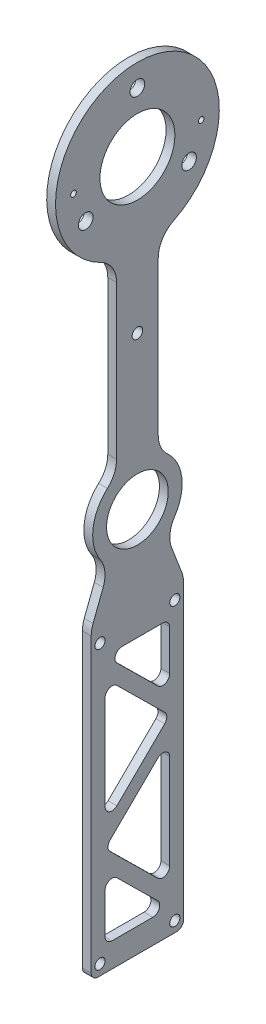
SolidWorks part; units mm, degrees
material "1060 Alloy"
ref_plane "Front Plane" through (0, 0, 0) normal (0, 0, 1) x (1, 0, 0)
ref_plane "Top Plane" through (0, 0, 0) normal (0, 1, 0) x (1, 0, 0)
ref_plane "Right Plane" through (0, 0, 0) normal (1, 0, 0) x (0, 0, -1)
sketch "Sketch1" plane through (0, 0, 0) normal (1, 0, 0) x (0, 0, -1)
  line L0 (-13.4747, 0) -> (13.4747, 0) construction
  line L1 (0, 0) -> (0, 23.8875) construction
  line L2 (-13.4747, 0) -> (-3.9926, 24.6295) construction
  line L3 (0, 35) -> (2.6946, 28.0008) construction
  line L4 (13.4747, 0) -> (-13.4747, 0) construction
  line L5 (20.7574, -5) -> (-20.7574, -5)
  line L6 (-20.7574, -5) -> (-10.1693, 22.5021)
  line L7 (1.1006, 46.0579) -> (6.6746, 31.5795) construction
  line L8 (0, 35) -> (0, 46.1125) construction
  line L9 (0, 35) -> (0, 46.1125) construction
  line L12 (-7.5, 35) -> (-7.5, 43.1999) construction
  line L13 (7.5, 35) -> (7.5, 43.1999) construction
  line L14 (-7.5, 35) -> (-7.5, 29.4356) construction
  line L15 (7.5, 35) -> (7.5, 29.4356) construction
  line L16 (-13.4747, 0) -> (13.4747, 0) construction
  line L17 (-13.4747, 0) -> (-13.4747, -100) construction
  line L18 (13.4747, 0) -> (13.4747, -100) construction
  line L19 (-13.4747, -100) -> (13.4747, -100) construction
  line L20 (-20.7574, -5) -> (20.7574, -5)
  line L21 (-20.7574, -5) -> (-20.7574, -103.81)
  line L22 (20.7574, -5) -> (20.7574, -103.81)
  line L23 (-20.7574, -103.81) -> (20.7574, -103.81)
  line L24 (-10.1693, 22.5021) -> (-8.2317, 27.535) construction
  line L25 (-7.5, 29.4356) -> (-6.6746, 31.5795) construction
  line L26 (-20.7574, -5) -> (0, 48.9165) construction
  line L27 (8.2317, 27.535) -> (10.1693, 22.5021) construction
  line L28 (10.1693, 22.5021) -> (20.7574, -5)
  line L29 (0, 48.9165) -> (20.7574, -5) construction
  line L30 (-7.5, 43.1999) -> (-7.5, 49.2605) construction
  line L31 (-7.5, 49.2605) -> (-7.5, 145)
  line L32 (7.5, 43.1999) -> (7.5, 49.2605) construction
  line L33 (7.5, 49.2605) -> (7.5, 145)
  line L34 (-1.1006, 46.0579) -> (0, 48.9165) construction
  line L35 (0, 46.1125) -> (0, 48.9165) construction
  line L36 (0, 48.9165) -> (0, 145) construction
  line L37 (0, 46.1125) -> (0, 48.9165) construction
  line L38 (0, 48.9165) -> (0, 145) construction
  line L39 (0, 48.9165) -> (1.1006, 46.0579) construction
  line L40 (-8.2317, 27.535) -> (-7.5, 29.4356) construction
  line L41 (-3.9926, 24.6295) -> (-2.6946, 28.0008) construction
  line L42 (-2.6946, 28.0008) -> (0, 35) construction
  line L43 (-13.4747, 0) -> (0, 35) construction
  line L44 (0, 23.8875) -> (0, 27.5) construction
  line L45 (0, 27.5) -> (0, 35) construction
  line L46 (2.6946, 28.0008) -> (3.9926, 24.6295) construction
  line L47 (3.9926, 24.6295) -> (13.4747, 0) construction
  line L48 (0, 35) -> (13.4747, 0) construction
  line L49 (7.5, 29.4356) -> (8.2317, 27.535) construction
  line L50 (6.6746, 31.5795) -> (7.5, 29.4356) construction
  line L51 (-6.6746, 31.5795) -> (-1.1006, 46.0579) construction
  circle A0 centre (-13.4747, 0) radius 1.8288
  circle A1 centre (0, 35) radius 11.1125
  circle A2 centre (13.4747, 0) radius 1.8288
  circle A3 centre (0, 145) radius 3 construction
  arc A6 (-7.5, 35) -> (-6.6746, 31.5795) centre (0, 35) ccw construction
  arc A7 (7.5, 145) -> (-7.5, 145) centre (0, 145) ccw
  circle A8 centre (-13.4747, -100) radius 1.8288
  circle A9 centre (13.4747, -100) radius 1.8288
  circle A10 centre (0, 145) radius 21.5 construction
  circle A11 centre (0, 166.5) radius 2.65
  circle A12 centre (-18.6195, 134.25) radius 2.65
  circle A13 centre (18.6195, 134.25) radius 2.65
  arc A14 (0, 166.5) -> (-18.6195, 134.25) centre (0, 145) ccw construction
  arc A15 (0, 166.5) -> (18.6195, 134.25) centre (0, 145) cw construction
  arc A16 (-18.6195, 134.25) -> (18.6195, 134.25) centre (0, 145) ccw construction
  circle A17 centre (0, 145) radius 13.5
  circle A18 centre (0, 145) radius 29.5
  arc A19 (10.1693, 22.5021) -> (7.5, 49.2605) centre (0, 35) ccw
  arc A20 (-10.1693, 22.5021) -> (-5.789, 19.9634) centre (0, 35) ccw construction
  circle A21 centre (0, 35) radius 16.1125 construction
  arc A22 (-5.789, 19.9634) -> (0, 18.8875) centre (0, 35) ccw construction
  arc A23 (0, 18.8875) -> (5.789, 19.9634) centre (0, 35) ccw construction
  arc A24 (5.789, 19.9634) -> (10.1693, 22.5021) centre (0, 35) ccw construction
  arc A25 (0, 51.1125) -> (-7.5, 49.2605) centre (0, 35) ccw construction
  arc A26 (-7.5, 49.2605) -> (-10.1693, 22.5021) centre (0, 35) ccw
  arc A27 (7.5, 49.2605) -> (0, 51.1125) centre (0, 35) ccw construction
  arc A28 (2.6946, 28.0008) -> (6.6746, 31.5795) centre (0, 35) ccw construction
  arc A29 (6.6746, 31.5795) -> (7.5, 35) centre (0, 35) ccw construction
  arc A30 (-2.6946, 28.0008) -> (0, 27.5) centre (0, 35) ccw construction
  arc A31 (0, 27.5) -> (2.6946, 28.0008) centre (0, 35) ccw construction
  arc A32 (-6.6746, 31.5795) -> (-2.6946, 28.0008) centre (0, 35) ccw construction
  point P4 (0, 0)
  point P14 (0, 90)
  point P34 (0, 145)
  dimension "D3" = 3.6576
  dimension "D4" = 22.225
  dimension "D7" = 6
  dimension "D11" = 43
  dimension "D12" = 5.3
  dimension "D13" = 27
  dimension "D14" = 59
  dimension "D1" = 26.9494
  dimension "D5" = 110
  dimension "D6" = 15
  dimension "D8" = 100
  dimension "D9" = 3.81
  dimension "D10" = 35
  dimension "D15" = 5
  dimension "D2" = 5
extrude "Boss-Extrude1" add sketch "Sketch1" along normal blind 3.175 contours L13 A18 L12 A17 A11 A12 A13 | L12 A18 L13 A17 | A18 L12 A6 L6 L7 L13 | L6 A6 L7 A1 | A6 L6 L5 L7 A2 A0 | A6 L14 L6 | A6 L7 L15 | L21 L23 L22 L5 A9 A8 region at (0, -54.1702, 0) region at (0, 46.4149, 0) region at (0, 124.037, 0) region at (0, 125.1222, -8.3276)
sketch "Sketch2" plane through (3.175, 0, 0) normal (1, 0, 0) x (0, 0, -1)
  line L0 (-11.645, -5) -> (11.645, -5) construction
  line L1 (-11.645, -95) -> (11.645, -95) construction
  line L2 (11.645, -95) -> (11.645, -5) construction
  line L3 (-11.645, -95) -> (-11.645, -5) construction
  line L6 (11.645, -38.5118) -> (-11.645, -61.4882) construction
  line L7 (11.645, -5) -> (-11.645, -5)
  line L8 (-11.645, -5) -> (11.645, -27.9764)
  line L9 (11.645, -27.9764) -> (11.645, -5)
  line L10 (-11.645, -12.0236) -> (11.645, -35)
  line L11 (11.645, -35) -> (-11.645, -57.9764)
  line L12 (-11.645, -57.9764) -> (-11.645, -35)
  line L13 (-11.645, -35) -> (-11.645, -12.0236)
  line L14 (-11.645, -72.0236) -> (-11.645, -95)
  line L15 (-11.645, -95) -> (11.645, -95)
  line L16 (11.645, -95) -> (-11.645, -72.0236)
  line L17 (11.645, -42.0236) -> (11.645, -65)
  line L18 (11.645, -65) -> (11.645, -87.9764)
  line L19 (11.645, -87.9764) -> (-11.645, -65)
  line L20 (-11.645, -65) -> (11.645, -42.0236)
  line L21 (16.645, -1056.0877) -> (16.645, 48943.9123) construction
  line L22 (-16.645, -1060.2922) -> (-16.645, 48939.7078) construction
  line L23 (16.645, 23.8875) -> (-16.645, 23.8875) construction
  line L24 (-20.7574, -103.81) -> (-16.645, -103.81)
  line L25 (-20.7574, -103.81) -> (-20.7574, 23.8875)
  line L26 (-16.645, -103.81) -> (-16.645, 23.8875)
  line L27 (-20.7574, 23.8875) -> (-16.645, 23.8875)
  line L28 (-20.7574, -103.81) -> (20.7574, -103.81) construction
  line L29 (20.7574, -103.81) -> (16.645, -103.81)
  line L30 (20.7574, -103.81) -> (20.7574, 23.8875)
  line L31 (16.645, -103.81) -> (16.645, 23.8875)
  line L32 (20.7574, 23.8875) -> (16.645, 23.8875)
  circle A0 centre (13.4747, 0) radius 1.8288 construction
  circle A1 centre (13.4747, -100) radius 1.8288 construction
  circle A2 centre (0, 35) radius 11.1125 construction
  point P6 (11.645, -50)
  point P10 (0, 23.8875)
  point P21 (0, -50)
  dimension "D1" = 33.29
  dimension "D2" = 5
  dimension "D3" = 5
  dimension "D4" = 5
  dimension "D5" = 5
  dimension "D6" = 2.5
  dimension "D8" = 5
  dimension "D7" = 2
extrude "Cut-Extrude1" cut sketch "Sketch2" against normal up to next
fillet "Fillet3" radius 2.5 14 edges at (1.5875, -57.9764, 11.645) (1.5875, -35, -11.645) (1.5875, -95, -11.645) (1.5875, -72.0236, 11.645) (1.5875, -95, 11.645) (1.5875, -27.9764, -11.645) (1.5875, -5, -11.645) (1.5875, -12.0236, 11.645) (1.5875, -5, 11.645) (1.5875, -87.9764, -11.645) (1.5875, -42.0236, -11.645) (1.5875, -65, 11.645) (1.5875, -103.81, -16.645) (1.5875, -103.81, 16.645)
fillet "Fillet4" radius 10 8 edges at (1.5875, 5.6818, 16.645) (1.5875, 116.4693, 7.5) (1.5875, 116.4693, -7.5) (1.5875, 49.2605, -7.5) (1.5875, 49.2605, 7.5) (1.5875, 22.5021, 10.1693) (1.5875, 22.5021, -10.1693) (1.5875, 5.6818, -16.645)
hole_wizard "M2.5x0.45 Tapped Hole1" positions "Sketch3" profile "Sketch4" tap size "M2.5x0.45" standard "ANSI Metric" end condition up to next
sketch "Sketch3" plane through (3.175, 0, 0) normal (1, 0, 0) x (0, 0, -1)
  line L0 (0, 166.5) -> (0, 145) construction
  line L2 (0, 145) -> (50000, 145) construction
  circle A0 centre (0, 145) radius 23.015 construction
  point P15 (-23.015, 145)
  point P17 (23.015, 145)
  dimension "D1" = 46.03
sketch "Sketch4" plane through (3.175, 145, -23.015) normal (0, 1, 0) x (0, 0, -1)
  line L0 (0, 0) -> (0, 3.175)
  line L1 (0, 3.175) -> (1.025, 3.175)
  line L2 (1.025, 3.175) -> (1.025, 0)
  line L5 (1.025, 0) -> (0, 0)
  line L11 (0, -6.35) -> (0, 107.95) construction
  dimension "Thru Tap Drill Dia." = 2.05
  dimension "Thru Tap Drill Depth" = 3.175
cosmetic thread "Hole Thread1" parameters "D2"=2.5
cosmetic thread "Hole Thread2" parameters "D2"=2.5
hole_wizard "#6 Clearance Hole1" positions "Sketch5" profile "Sketch6" hole size "#6" standard "ANSI Inch" end condition through all
sketch "Sketch5" plane through (3.175, 0, 0) normal (1, 0, 0) x (0, 0, -1)
  circle A0 centre (0, 35) radius 11.1125 construction
  point P0 (0, 90)
  dimension "D1" = 55
sketch "Sketch6" plane through (3.175, 90, 0) normal (0, 1, 0) x (0, 0, -1)
  line L0 (0, 0) -> (0, 3.175)
  line L1 (0, 3.175) -> (1.8986, 3.175)
  line L2 (1.8986, 3.175) -> (1.8986, 0)
  line L5 (1.8986, 0) -> (0, 0)
  line L11 (0, -6.35) -> (0, 107.95) construction
  dimension "Thru Hole Dia." = 3.7973
  dimension "Thru Hole Depth" = 3.175
